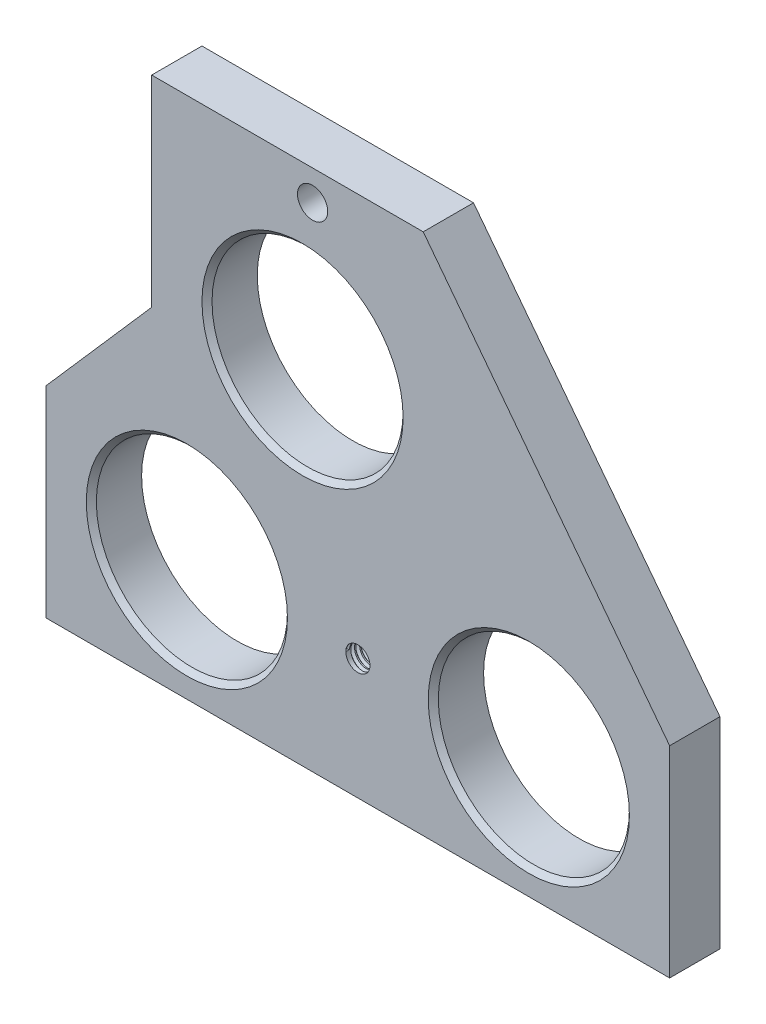
SolidWorks part; units mm, degrees
material "Stop 1060"
ref_plane "Płaszczyzna przednia" through (0, 0, 0) normal (0, 0, 1) x (1, 0, 0)
ref_plane "Płaszczyzna górna" through (0, 0, 0) normal (0, 1, 0) x (1, 0, 0)
ref_plane "Płaszczyzna prawa" through (0, 0, 0) normal (1, 0, 0) x (0, 0, -1)
sketch "Szkic1" plane through (0, 0, 0) normal (0, 0, 1) x (1, 0, 0)
  line L0 (-14, -12) -> (-14, 8)
  line L1 (-3.5, 40) -> (23.5, 40)
  line L2 (48, 8) -> (48, -12)
  line L3 (48, -12) -> (-14, -12)
  line L4 (-3.5, 40) -> (-3.5, 20)
  line L6 (-14, 8) -> (-3.5, 20)
  line L7 (23.5, 40) -> (48, 8)
  circle A0 centre (0, 0) radius 9.5
  circle A1 centre (34, 0) radius 9.5
  circle A2 centre (11.5, 23) radius 9.5
  circle A3 centre (12.5, 37) radius 1.5
  circle A4 centre (17, 0) radius 1.2
  point P18 (0, 0)
  dimension "D1" = 19
  dimension "D2" = 19
  dimension "D3" = 19
  dimension "D4" = 34
  dimension "D5" = 23
  dimension "D6" = 11.5
  dimension "D8" = 14
  dimension "D9" = 14
  dimension "D10" = 3
  dimension "D11" = 12
  dimension "D17" = 3
  dimension "D18" = 16
  dimension "D19" = 3
  dimension "D20" = 17
  dimension "D21" = 23
  dimension "D22" = 2.4
  dimension "D7" = 12
  dimension "D12" = 20
  dimension "D13" = 27
  dimension "D14" = 20
  dimension "D15" = 20
  dimension "D16" = 24.5
extrude "Dodanie-wyciągnięcie1" add sketch "Szkic1" along normal blind 5
chamfer "Sfazowanie2" distance 0.5 angle 45 3 edges at (43.5, 0, 5) (21, 23, 5) (9.5, 0, 5)
thread "Gwint1" pitch 0.5 method cut profile "Profil gwintu1" start angle 0, offset 0, length 10, pitch 0.5, diameter 2.4
ref_plane "Płaszczyzna1" through (15.8, 0, 5) normal (0, -1, 0) x (-1, 0, 0)
sketch "Profil gwintu1" plane through (15.8, 0, 5) normal (0, -1, 0) x (-1, 0, 0)
  line L0 (0, 0) -> (0, 0.5) construction
  line L1 (0, 0) -> (0.2706, 0.1562)
  line L2 (0.2706, 0.1562) -> (0.2706, 0.2187)
  line L3 (0.2706, 0.2187) -> (0, 0.375)
  line L4 (0.2706, 0.1875) -> (0, 0.1875) construction
  line L11 (0, 0) -> (0, 0.375)
  point P2 (0, 0)
  dimension "Pitch" = 0.5
  dimension "Profile_Angle" = 60
  dimension "Profile_Land" = 0.0625
  dimension "Profile_Height" = 0.2706
